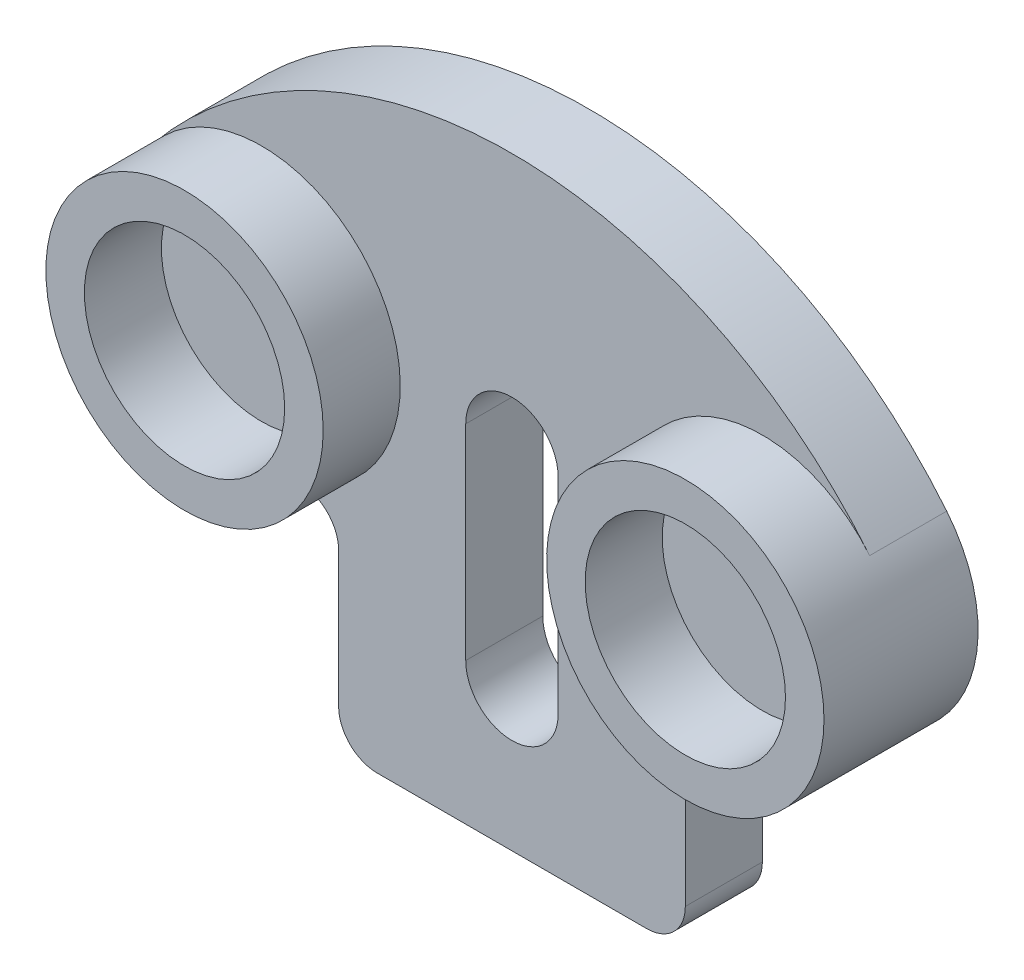
SolidWorks part; units mm, degrees
ref_plane "Front Plane" through (0, 0, 0) normal (0, 0, 1) x (1, 0, 0)
ref_plane "Top Plane" through (0, 0, 0) normal (0, 1, 0) x (1, 0, 0)
ref_plane "Right Plane" through (0, 0, 0) normal (1, 0, 0) x (0, 0, -1)
sketch "Sketch1" plane through (0, 0, 0) normal (0, 0, 1) x (1, 0, 0)
  line L0 (-6, 0) -> (-6, 26.6036)
  line L1 (6, 26.6036) -> (6, 0)
  line L2 (0, -43.9085) -> (0, 43.9085) construction
  line L3 (17.5, -18.3964) -> (-17.5, -18.3964)
  line L4 (-22.5, -13.3964) -> (-22.5, 4.1536)
  line L5 (-32.5, 26.6036) -> (0, 26.6036) construction
  line L6 (22.5, -13.3964) -> (22.5, 4.1536)
  arc A0 (-6, 0) -> (6, 0) centre (0, 0) ccw
  arc A1 (6, 26.6036) -> (-6, 26.6036) centre (0, 26.6036) ccw
  circle A2 centre (-32.5, 26.6036) radius 18
  circle A3 centre (-32.5, 26.6036) radius 13
  arc A4 (46.4286, 38.0051) -> (-46.4286, 38.0051) centre (0, 0) ccw
  arc A5 (-17.5, -18.3964) -> (-22.5, -13.3964) centre (-17.5, -13.3964) cw
  arc A6 (-22.5, 4.1536) -> (-28.587, 9.034) centre (-27.5, 4.1536) ccw
  arc A7 (17.5, -18.3964) -> (22.5, -13.3964) centre (17.5, -13.3964) ccw
  arc A8 (22.5, 4.1536) -> (28.587, 9.034) centre (27.5, 4.1536) cw
  circle A9 centre (32.5, 26.6036) radius 13
  circle A10 centre (32.5, 26.6036) radius 18
  point P10 (0, 0)
  point P24 (0, -18.3964)
  dimension "D1" = 12
  dimension "D2" = 5
  dimension "D3" = 5
  dimension "D4" = 5
  dimension "D6" = 36
  dimension "D9" = 60
  dimension "D5" = 22.5
  dimension "D7" = 45
  dimension "D8" = 32.5
extrude "Boss-Extrude1" add sketch "Sketch1" along normal blind 10 contours A8 A10 A4 A2 A6 L4 A5 L3 A7 L6 A1 L1 A0 L0 | A10 A4 A9 | A9 | A2 region at (0, -17.1812, 0) region at (17.6068, 35.7754, 0) region at (32.5, 26.6036, 0)
extrude "Boss-Extrude2" add sketch "Sketch1<3>" along normal blind 20 contours A2 A4 A3 | A10 A4 A9 region at (17.6068, 35.7754, 0) region at (-47.3932, 17.4317, 0)
sketch "Sketch1<3>" plane through (0, 0, 0) normal (0, 0, 1) x (1, 0, 0) same geometry as "Sketch1"
